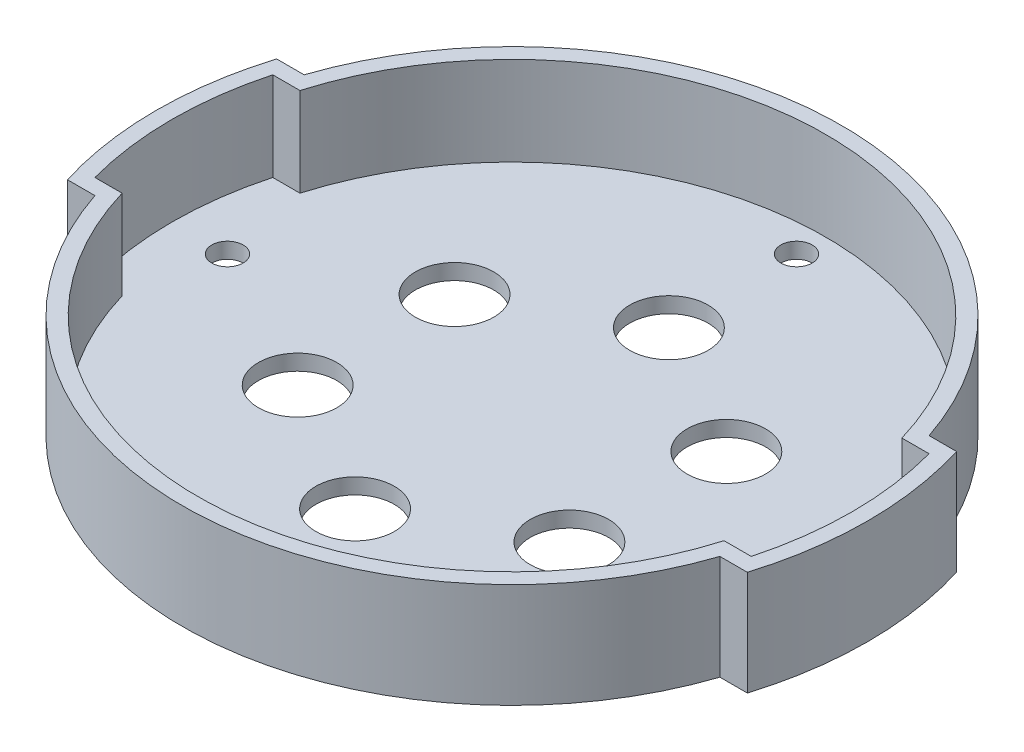
SolidWorks part; units mm, degrees
ref_plane "Front Plane" through (0, 0, 0) normal (0, 0, 1) x (1, 0, 0)
ref_plane "Top Plane" through (0, 0, 0) normal (0, 1, 0) x (1, 0, 0)
ref_plane "Right Plane" through (0, 0, 0) normal (1, 0, 0) x (0, 0, -1)
sketch "Sketch1" plane through (0, 0, 0) normal (0, 1, 0) x (1, 0, 0)
  circle A0 centre (0, 0) radius 68
  dimension "D1" = 136
extrude "Boss-Extrude1" add sketch "Sketch1" along normal blind 20
sketch "Sketch2" plane through (0, 20, 0) normal (0, 1, 0) x (1, 0, 0)
  line L1 (0, 37.0764) -> (0, -27.4787) construction
  line L5 (-59.7411, -20) -> (-64.9923, -20)
  line L6 (-59.7411, 20) -> (-64.9923, 20)
  line L7 (59.7411, -20) -> (64.9923, -20)
  line L8 (59.7411, 20) -> (64.9923, 20)
  line L9 (-28.4675, 0) -> (19.3594, 0) construction
  arc A0 (-59.7411, -20) -> (59.7411, -20) centre (0, 0) ccw
  arc A1 (-64.9923, -20) -> (64.9923, -20) centre (0, 0) ccw
  circle A2 centre (0, 0) radius 68 construction
  arc A3 (59.7411, 20) -> (-59.7411, 20) centre (0, 0) ccw
  arc A4 (64.9923, 20) -> (-64.9923, 20) centre (0, 0) ccw
  dimension "D1" = 126
  dimension "D2" = 40
  dimension "D3" = 40
extrude "Cut-Extrude1" cut sketch "Sketch2" against normal up to surface (20 mm away) up to face at (0, 0, 68)
shell "Shell1" thickness 3 removed face at (0, 20, 0)
sketch "Sketch3" plane through (0, 0, 0) normal (0, -1, 0) x (1, 0, 0)
  line L0 (-78.2757, 0) -> (93.912, 0) construction
  line L1 (0, -51.8142) -> (0, 50.9292) construction
  circle A0 centre (-54.4, 0) radius 3
  circle A1 centre (54.4, 0) radius 3
  circle A2 centre (0, 30) radius 7.5
  circle A3 centre (25.9808, 15) radius 7.5
  circle A4 centre (25.9808, -15) radius 7.5
  circle A5 centre (0, -30) radius 7.5
  circle A6 centre (-25.9808, -15) radius 7.5
  circle A7 centre (-25.9808, 15) radius 7.5
  circle A8 centre (0, -54.4) radius 3
  circle A9 centre (0, 54.4) radius 3
  point P24 (0, 0)
  dimension "D1" = 6
  dimension "D2" = 6
  dimension "D5" = 15
  dimension "D9" = 6
  dimension "D10" = 6
  dimension "D3" = 54.4
  dimension "D4" = 54.4
  dimension "D6" = 30
  dimension "D8" = 30
  dimension "D11" = 54.4
  dimension "D12" = 54.4
  dimension "D7" = 6
extrude "Cut-Extrude2" cut sketch "Sketch3" against normal through all both and the other way through all
